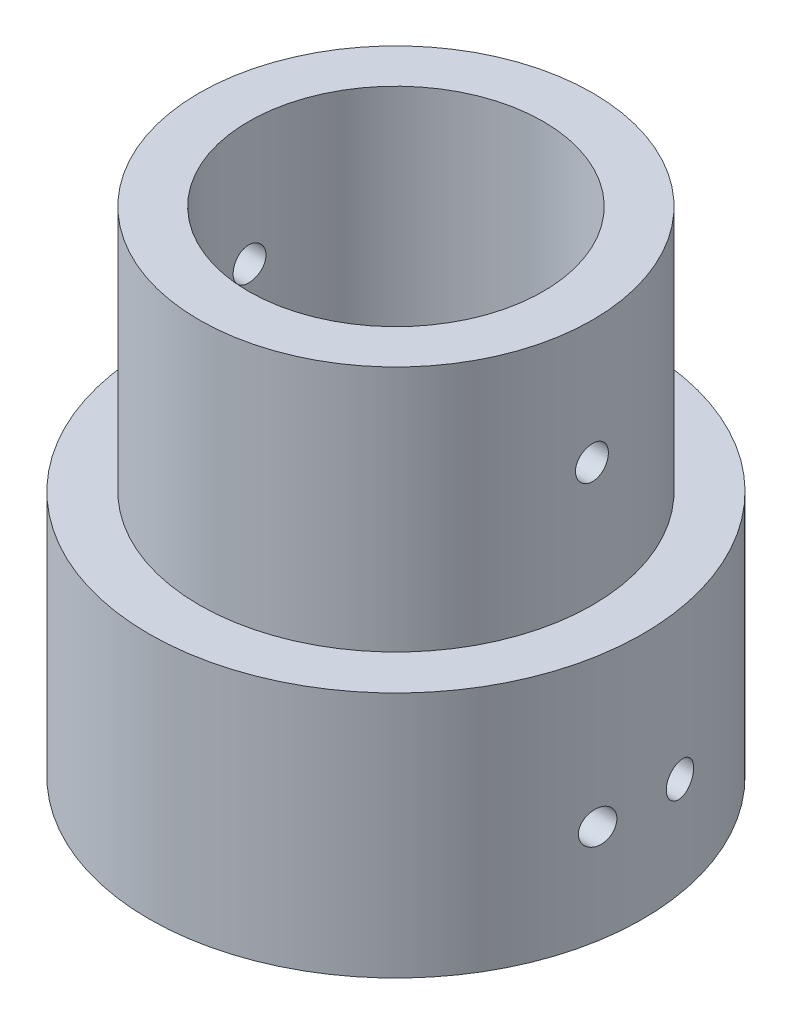
SolidWorks part; units mm, degrees
ref_plane "Front Plane" through (0, 0, 0) normal (0, 0, 1) x (1, 0, 0)
ref_plane "Top Plane" through (0, 0, 0) normal (0, 1, 0) x (1, 0, 0)
ref_plane "Right Plane" through (0, 0, 0) normal (1, 0, 0) x (0, 0, -1)
sketch "Sketch1" plane through (0, 0, 0) normal (0, 1, 0) x (1, 0, 0)
  circle A0 centre (0, 0) radius 15
  dimension "D1" = 30
extrude "Boss-Extrude1" add sketch "Sketch1" along normal blind 15
sketch "Sketch2" plane through (0, 15, 0) normal (0, 1, 0) x (1, 0, 0)
  circle A0 centre (0, 0) radius 8.95
  circle A1 centre (0, 0) radius 11.95
  dimension "D1" = 17.9
  dimension "D2" = 23.9
extrude "Boss-Extrude2" add sketch "Sketch2" along normal blind 15 and the other way blind 3
sketch "Sketch3" plane through (0, 0, 0) normal (1, 0, 0) x (0, 0, -1)
  line L0 (0, 30) -> (0, 22.5) construction
  line L1 (11.95, 30) -> (-11.95, 30) construction
  line L2 (-15, 0) -> (15, 0) construction
  circle A0 centre (0, 22.5) radius 1
  circle A2 centre (-2.5, 6) radius 1
  circle A3 centre (2.5, 6) radius 1
  dimension "D1" = 2
  dimension "D2" = 7.5
  dimension "D3" = 5
  dimension "D4" = 6
extrude "Cut-Extrude1" cut sketch "Sketch3" against normal through all and the other way through all
sketch "Sketch4" plane through (0, 0, 0) normal (1, 0, 0) x (0, 0, -1)
  line L0 (0, -40) -> (0, 0) construction
  line L1 (11, 0) -> (-11, 0)
  line L2 (11, 0) -> (11, -12)
  line L4 (-11, 0) -> (-11, -12)
  line L5 (-15, 0) -> (15, 0) construction
  circle A0 centre (0, -40) radius 11
  arc A1 (-15, -20) -> (15, -20) centre (0, -40) ccw
  arc A2 (-11, -12) -> (-15, -20) centre (-21, -12) cw
  arc A3 (11, -12) -> (15, -20) centre (21, -12) ccw
  point P1 (0, -50.781)
  dimension "D3" = 22
  dimension "D4" = 50
  dimension "D5" = 10
  dimension "D1" = 22
  dimension "D2" = 40
extrude "Boss-Extrude3" add sketch "Sketch4" along normal blind 5
hole_wizard "M3 Clearance Hole1" positions "Sketch6" profile "Sketch7" hole size "M3" standard "ANSI Metric" end condition through all
sketch "Sketch6" plane through (5, 0, 0) normal (1, 0, 0) x (0, 0, -1)
  line L0 (10.6066, -50.6066) -> (-10.6066, -29.3934) construction
  line L3 (-10.6066, -50.6066) -> (10.6066, -29.3934) construction
  circle A0 centre (0, -40) radius 15 construction
  circle A1 centre (0, -40) radius 11 construction
  point P0 (10.6066, -50.6066)
  point P2 (-10.6066, -50.6066)
  point P4 (-10.6066, -29.3934)
  point P6 (10.6066, -29.3934)
  point P28 (0, 0)
  dimension "D2" = 30
  dimension "D1" = 90
sketch "Sketch7" plane through (5, -50.6066, -10.6066) normal (0, 1, 0) x (0, 0, -1)
  line L0 (0, 0) -> (0, 20)
  line L1 (0, 20) -> (1.7, 20)
  line L2 (1.7, 20) -> (1.7, 0)
  line L5 (1.7, 0) -> (0, 0)
  line L11 (0, -6.35) -> (0, 107.95) construction
  dimension "Thru Hole Dia." = 3.4
  dimension "Thru Hole Depth" = 20
sketch "Sketch8" plane through (0, 0, 0) normal (0, -1, 0) x (1, 0, 0)
  circle A0 centre (0, 0) radius 26.296
extrude "Cut-Extrude2" cut sketch "Sketch8" along normal through all
sketch "Sketch9" plane through (0, 0, 0) normal (0, -1, 0) x (1, 0, 0)
  line L1 (0, 7.75) -> (6.2, 7.75)
  line L2 (0, 7.75) -> (0, -7.75)
  line L3 (0, -7.75) -> (6.2, -7.75)
  line L4 (6.2, 7.75) -> (6.2, -7.75)
  dimension "D1" = 15.5
  dimension "D2" = 6.2
extrude "Cut-Extrude3" cut sketch "Sketch9" against normal blind 12
